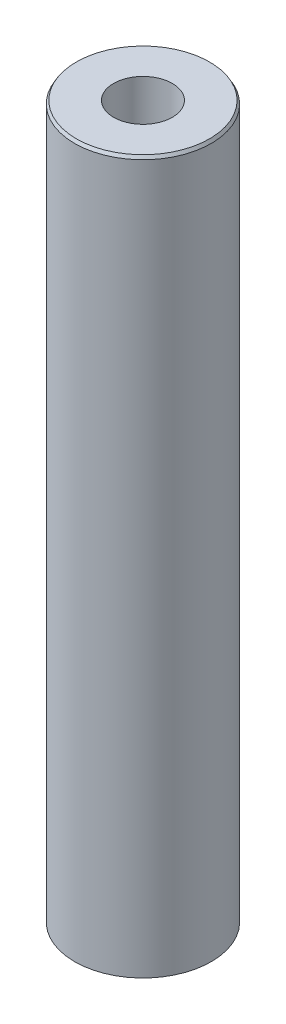
SolidWorks part; units mm, degrees
ref_plane "Front Plane" through (0, 0, 0) normal (0, 0, 1) x (1, 0, 0)
ref_plane "Top Plane" through (0, 0, 0) normal (0, 1, 0) x (1, 0, 0)
ref_plane "Right Plane" through (0, 0, 0) normal (1, 0, 0) x (0, 0, -1)
sketch "Sketch1" plane through (0, 0, 0) normal (0, 1, 0) x (1, 0, 0)
  circle A0 centre (0, 0) radius 57.5
  dimension "SHAFT_OD" = 115
extrude "Boss-Extrude1" add sketch "Sketch1" along normal blind 600
sketch "Sketch2" plane through (0, 0, 0) normal (0, 1, 0) x (1, 0, 0)
  circle A0 centre (0, 0) radius 24.6938
  dimension "BORE_D" = 49.3875
extrude "Cut-Extrude1" cut sketch "Sketch2" along normal through all
chamfer "Chamfer1" distance 2.6044 angle 30 2 edges at (0, 600, 57.5) (0, 0, 57.5) first distance on face at (0, 600, 57.5) first distance on face at (0, 0, 24.6938)
